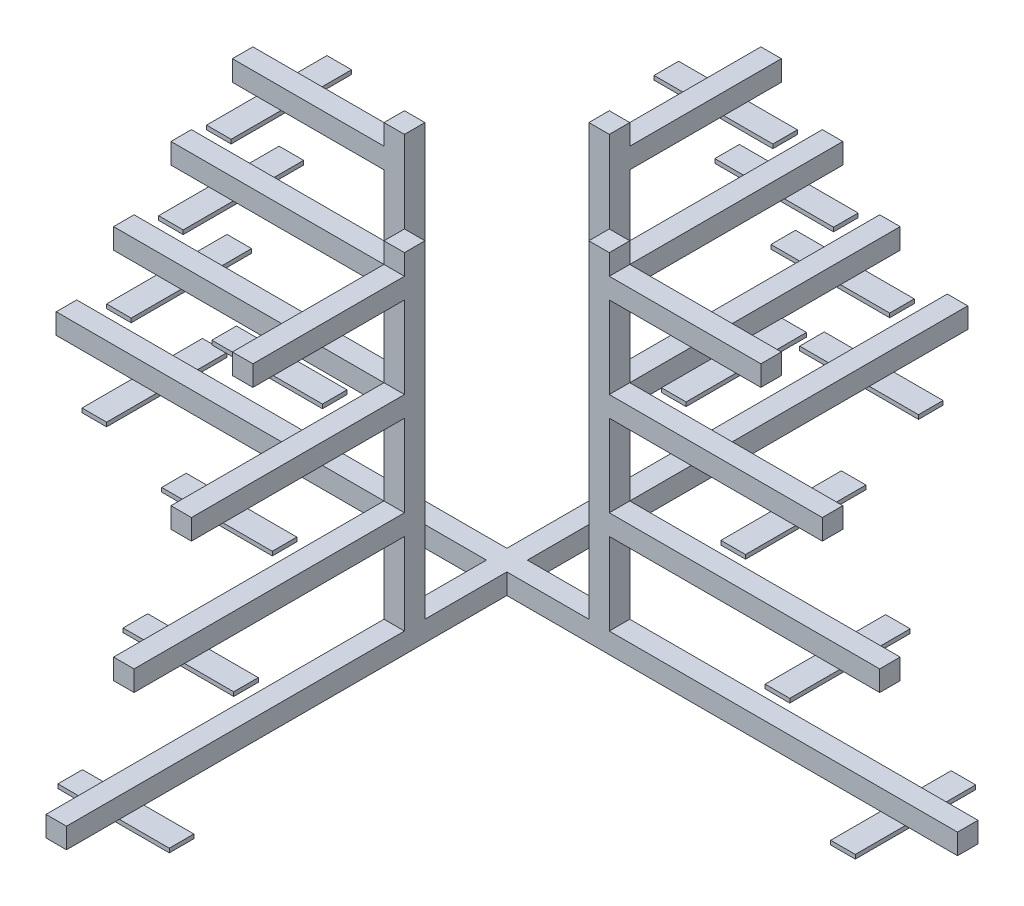
SolidWorks part; units mm, degrees
ref_plane "Front Plane" through (0, 0, 0) normal (0, 0, 1) x (1, 0, 0)
ref_plane "Top Plane" through (0, 0, 0) normal (0, 1, 0) x (1, 0, 0)
ref_plane "Right Plane" through (0, 0, 0) normal (1, 0, 0) x (0, 0, -1)
sketch "Sketch3" plane through (0, 0, 0) normal (0, 0, 1) x (1, 0, 0)
  line L1 (-12.5, 12.5) -> (12.5, 12.5)
  line L2 (-12.5, 12.5) -> (-12.5, -12.5)
  line L3 (-12.5, -12.5) -> (12.5, -12.5)
  line L4 (12.5, 12.5) -> (12.5, -12.5)
  line L5 (-12.5, 12.5) -> (12.5, -12.5) construction
  line L6 (-12.5, -12.5) -> (12.5, 12.5) construction
  point P0 (0, 0)
  dimension "D1" = 25
  dimension "D2" = 25
extrude "Boss-Extrude2" add sketch "Sketch3" along normal mid plane 1100
sketch "Sketch5" plane through (12.5, 0, 0) normal (1, 0, 0) x (0, 0, -1)
  line L0 (-550, -12.5) -> (550, -12.5) construction
  line L1 (-12.5, 12.5) -> (12.5, 12.5)
  line L2 (-12.5, 12.5) -> (-12.5, -12.5)
  line L3 (-12.5, -12.5) -> (12.5, -12.5)
  line L4 (12.5, 12.5) -> (12.5, -12.5)
  line L5 (-12.5, 12.5) -> (12.5, -12.5) construction
  line L6 (-12.5, -12.5) -> (12.5, 12.5) construction
  point P0 (0, 0)
  dimension "D1" = 25
extrude "Boss-Extrude3" add sketch "Sketch5" along normal mid plane 1100
sketch "Sketch7" plane through (0, 12.5, 0) normal (0, 1, 0) x (1, 0, 0)
  line L0 (-12.5, -12.5) -> (12.5, -12.5) construction
  line L1 (12.5, -12.5) -> (12.5, 12.5) construction
  line L2 (12.5, 12.5) -> (-12.5, 12.5) construction
  line L3 (-12.5, 12.5) -> (-12.5, -12.5) construction
  line L4 (-12.5, -12.5) -> (-12.5, -112.5)
  line L5 (-12.5, -550) -> (-12.5, -12.5) construction
  line L6 (-12.5, 12.5) -> (-12.5, 112.5)
  line L7 (-12.5, 12.5) -> (-12.5, 550) construction
  line L8 (-12.5, 112.5) -> (12.5, 112.5)
  line L9 (12.5, 12.5) -> (12.5, 550) construction
  line L10 (12.5, 112.5) -> (12.5, 137.5)
  line L11 (12.5, 137.5) -> (-12.5, 137.5)
  line L12 (-12.5, 137.5) -> (-12.5, 112.5)
  line L13 (-12.5, -112.5) -> (12.5, -112.5)
  line L14 (12.5, -550) -> (12.5, -12.5) construction
  line L15 (12.5, -112.5) -> (12.5, -137.5)
  line L16 (12.5, -137.5) -> (-12.5, -137.5)
  line L17 (-12.5, -137.5) -> (-12.5, -112.5)
  line M11 (12.5, -550) -> (12.5, -12.5)
  line M15 (12.5, 12.5) -> (12.5, 550)
  line M17 (-12.5, 550) -> (-12.5, 12.5)
  line M21 (-12.5, -12.5) -> (-12.5, -550)
  dimension "D1" = 100
  dimension "D2" = 100
  dimension "D3" = 25
  dimension "D4" = 25
extrude "Boss-Extrude4" add sketch "Sketch7" along normal blind 400 contours L16 L13 M11 M21 | L11 L8 M15 M17 region at (0, 12.5, -125) region at (0, 12.5, 125)
sketch "Sketch8" plane through (0, 12.5, 0) normal (0, 1, 0) x (1, 0, 0)
  line L0 (-12.5, -12.5) -> (-112.5, -12.5)
  line L1 (-12.5, -12.5) -> (-537.5, -12.5) construction
  line L2 (12.5, -12.5) -> (112.5, -12.5)
  line L3 (562.5, -12.5) -> (12.5, -12.5) construction
  line L4 (-112.5, -12.5) -> (-112.5, 12.5)
  line L5 (-12.5, 12.5) -> (-537.5, 12.5) construction
  line L6 (-112.5, 12.5) -> (-137.5, 12.5)
  line L7 (-137.5, 12.5) -> (-137.5, -12.5)
  line L8 (-137.5, -12.5) -> (-112.5, -12.5)
  line L9 (112.5, -12.5) -> (112.5, 12.5)
  line L10 (562.5, 12.5) -> (12.5, 12.5) construction
  line L11 (112.5, 12.5) -> (137.5, 12.5)
  line L12 (137.5, 12.5) -> (137.5, -12.5)
  line L13 (137.5, -12.5) -> (112.5, -12.5)
  line M8 (12.5, -12.5) -> (562.5, -12.5)
  line M10 (562.5, 12.5) -> (12.5, 12.5)
  line M14 (-12.5, 12.5) -> (-537.5, 12.5)
  line M16 (-537.5, -12.5) -> (-12.5, -12.5)
  dimension "D1" = 100
  dimension "D2" = 100
  dimension "D3" = 25
  dimension "D4" = 25
extrude "Boss-Extrude5" add sketch "Sketch8" along normal blind 400 contours L12 L9 M10 M8 | L7 L4 M14 M16 region at (-125, 12.5, 0) region at (125, 12.5, 0)
sketch "Sketch9" plane through (0, 0, 137.5) normal (0, 0, 1) x (1, 0, 0)
  line L0 (12.5, 12.5) -> (12.5, 112.5)
  line L1 (12.5, 412.5) -> (12.5, 12.5) construction
  line L2 (12.5, 112.5) -> (-12.5, 112.5)
  line L3 (-12.5, 412.5) -> (-12.5, 12.5) construction
  line L4 (-12.5, 112.5) -> (-12.5, 137.5)
  line L5 (-12.5, 137.5) -> (12.5, 137.5)
  line L6 (12.5, 137.5) -> (12.5, 112.5)
  line L7 (12.5, 137.5) -> (12.5, 237.5)
  line L8 (12.5, 237.5) -> (-12.5, 237.5)
  line L9 (-12.5, 237.5) -> (-12.5, 262.5)
  line L10 (-12.5, 262.5) -> (12.5, 262.5)
  line L11 (12.5, 262.5) -> (12.5, 237.5)
  line L12 (12.5, 262.5) -> (12.5, 362.5)
  line L13 (12.5, 362.5) -> (-12.5, 362.5)
  line L14 (-12.5, 362.5) -> (-12.5, 387.5)
  line L15 (-12.5, 387.5) -> (12.5, 387.5)
  line L16 (12.5, 387.5) -> (12.5, 362.5)
  line L17 (12.5, 262.5) -> (12.5, 237.5)
  line M17 (12.5, 12.5) -> (12.5, 412.5)
  line M19 (-12.5, 412.5) -> (-12.5, 12.5)
  dimension "D1" = 100
  dimension "D2" = 25
  dimension "D3" = 100
  dimension "D4" = 25
  dimension "D5" = 100
  dimension "D6" = 25
extrude "Boss-Extrude7" add sketch "Sketch9" along normal blind 260 contours L10 L8 M19 M17 region at (0, 250, 137.5)
extrude "Boss-Extrude8" add sketch "Sketch9<5>" along normal blind 330 contours L5 L2 M19 M17 region at (0, 125, 137.5)
sketch "Sketch9<5>" plane through (0, 0, 137.5) normal (0, 0, 1) x (1, 0, 0) same geometry as "Sketch9"
extrude "Boss-Extrude10" add sketch "Sketch9<8>" along normal blind 185 contours L15 L13 M19 M17 region at (0, 375, 137.5)
sketch "Sketch9<8>" plane through (0, 0, 137.5) normal (0, 0, 1) x (1, 0, 0) same geometry as "Sketch9"
sketch "Sketch11" plane through (-137.5, 0, 0) normal (-1, 0, 0) x (0, 0, 1)
  line L0 (12.5, 12.5) -> (12.5, 112.5)
  line L1 (12.5, 412.5) -> (12.5, 12.5) construction
  line L2 (12.5, 112.5) -> (-12.5, 112.5)
  line L3 (-12.5, 412.5) -> (-12.5, 12.5) construction
  line L4 (-12.5, 112.5) -> (-12.5, 137.5)
  line L5 (-12.5, 137.5) -> (12.5, 137.5)
  line L6 (12.5, 137.5) -> (12.5, 112.5)
  line L7 (12.5, 137.5) -> (12.5, 237.5)
  line L8 (12.5, 237.5) -> (-12.5, 237.5)
  line L9 (-12.5, 237.5) -> (-12.5, 262.5)
  line L10 (-12.5, 262.5) -> (12.5, 262.5)
  line L11 (12.5, 262.5) -> (12.5, 237.5)
  line L12 (12.5, 362.5) -> (-12.5, 362.5)
  line L13 (-12.5, 362.5) -> (-12.5, 387.5)
  line L14 (-12.5, 387.5) -> (12.5, 387.5)
  line L15 (12.5, 387.5) -> (12.5, 362.5)
  line M16 (12.5, 12.5) -> (12.5, 412.5)
  line M18 (-12.5, 412.5) -> (-12.5, 12.5)
  dimension "D1" = 100
  dimension "D2" = 25
  dimension "D3" = 100
  dimension "D4" = 25
  dimension "D5" = 25
  dimension "D6" = 100
extrude "Boss-Extrude11" add sketch "Sketch11" along normal blind 185 contours L14 L12 M18 M16 region at (-137.5, 375, 0)
extrude "Boss-Extrude12" add sketch "Sketch11<5>" along normal blind 260 contours L10 L8 M18 M16 region at (-137.5, 250, 0)
sketch "Sketch11<5>" plane through (-137.5, 0, 0) normal (-1, 0, 0) x (0, 0, 1) same geometry as "Sketch11"
extrude "Boss-Extrude13" add sketch "Sketch11<6>" along normal blind 330 contours L5 L2 M18 M16 region at (-137.5, 125, 0)
sketch "Sketch11<6>" plane through (-137.5, 0, 0) normal (-1, 0, 0) x (0, 0, 1) same geometry as "Sketch11"
sketch "Sketch12" plane through (0, 0, -137.5) normal (0, 0, -1) x (-1, 0, 0)
  line L0 (12.5, 112.5) -> (-12.5, 112.5)
  line L2 (12.5, 137.5) -> (-12.5, 137.5)
  line L3 (-12.5, 137.5) -> (-12.5, 112.5)
  line L4 (12.5, 137.5) -> (12.5, 112.5)
  line L5 (12.5, 237.5) -> (-12.5, 237.5)
  line L6 (-12.5, 412.5) -> (-12.5, 12.5) construction
  line L7 (-12.5, 237.5) -> (-12.5, 262.5)
  line L8 (-12.5, 262.5) -> (12.5, 262.5)
  line L9 (12.5, 262.5) -> (12.5, 237.5)
  line L10 (12.5, 362.5) -> (-12.5, 362.5)
  line L11 (-12.5, 362.5) -> (-12.5, 387.5)
  line L12 (-12.5, 387.5) -> (12.5, 387.5)
  line L13 (12.5, 387.5) -> (12.5, 362.5)
  line M2 (12.5, 12.5) -> (12.5, 412.5)
  line M4 (-12.5, 412.5) -> (-12.5, 12.5)
extrude "Boss-Extrude14" add sketch "Sketch12" along normal blind 185 contours L12 L10 M4 M2 region at (0, 375, -137.5)
extrude "Boss-Extrude15" add sketch "Sketch12<3>" along normal blind 260 contours L8 L5 M4 M2 region at (0, 250, -137.5)
sketch "Sketch12<3>" plane through (0, 0, -137.5) normal (0, 0, -1) x (-1, 0, 0) same geometry as "Sketch12"
extrude "Boss-Extrude16" add sketch "Sketch12<4>" along normal blind 330 contours L2 L0 M2 M4 region at (0, 125, -137.5)
sketch "Sketch12<4>" plane through (0, 0, -137.5) normal (0, 0, -1) x (-1, 0, 0) same geometry as "Sketch12"
sketch "Sketch13" plane through (137.5, 0, 0) normal (1, 0, 0) x (0, 0, -1)
  line L0 (12.5, 112.5) -> (-12.5, 112.5)
  line L1 (-12.5, 412.5) -> (-12.5, 12.5) construction
  line L2 (-12.5, 112.5) -> (-12.5, 137.5)
  line L3 (-12.5, 137.5) -> (12.5, 137.5)
  line L4 (12.5, 412.5) -> (12.5, 12.5) construction
  line L5 (12.5, 137.5) -> (12.5, 112.5)
  line L6 (12.5, 237.5) -> (12.5, 262.5)
  line L7 (12.5, 262.5) -> (-12.5, 262.5)
  line L8 (-12.5, 262.5) -> (-12.5, 237.5)
  line L9 (-12.5, 237.5) -> (12.5, 237.5)
  line L10 (-12.5, 362.5) -> (12.5, 362.5)
  line L11 (12.5, 362.5) -> (12.5, 387.5)
  line L12 (12.5, 387.5) -> (-12.5, 387.5)
  line L13 (-12.5, 387.5) -> (-12.5, 362.5)
  line M6 (12.5, 12.5) -> (12.5, 412.5)
  line M8 (-12.5, 412.5) -> (-12.5, 12.5)
extrude "Boss-Extrude17" add sketch "Sketch13" along normal blind 330 contours L3 L0 M8 M6 region at (137.5, 125, 0)
extrude "Boss-Extrude18" add sketch "Sketch13<3>" along normal blind 260 contours L9 L7 M8 M6 region at (137.5, 250, 0)
sketch "Sketch13<3>" plane through (137.5, 0, 0) normal (1, 0, 0) x (0, 0, -1) same geometry as "Sketch13"
extrude "Boss-Extrude19" add sketch "Sketch13<4>" along normal blind 185 contours L12 L13 L10 L11
sketch "Sketch13<4>" plane through (137.5, 0, 0) normal (1, 0, 0) x (0, 0, -1) same geometry as "Sketch13"
sketch "Sketch15" plane through (12.5, 0, 0) normal (1, 0, 0) x (0, 0, -1)
  line L0 (-485.5198, -12.5) -> (-485.5198, -17.5)
  line L1 (-550, -12.5) -> (-12.5, -12.5) construction
  line L2 (-485.5198, -17.5) -> (-455.5198, -17.5)
  line L3 (-455.5198, -17.5) -> (-455.5198, -12.5)
  line L4 (-455.5198, -12.5) -> (-485.5198, -12.5)
  dimension "D1" = 5
  dimension "D2" = 30
extrude "Boss-Extrude21" add sketch "Sketch15" along normal blind 61 and the other way blind 75
sketch "Sketch16" plane through (12.5, 0, 0) normal (1, 0, 0) x (0, 0, -1)
  line L0 (-405.908, 112.5) -> (-405.908, 107.5)
  line L1 (-467.5, 112.5) -> (-137.5, 112.5) construction
  line L2 (-405.908, 107.5) -> (-375.908, 107.5)
  line L3 (-375.908, 107.5) -> (-375.908, 112.5)
  line L4 (-375.908, 112.5) -> (-405.908, 112.5)
  line L5 (-358.8325, 237.5) -> (-358.8325, 232.5)
  line L6 (-397.5, 237.5) -> (-137.5, 237.5) construction
  line L7 (-358.8325, 232.5) -> (-328.8325, 232.5)
  line L8 (-328.8325, 232.5) -> (-328.8325, 237.5)
  line L9 (-328.8325, 237.5) -> (-358.8325, 237.5)
  line L10 (-297.5952, 362.5) -> (-297.5952, 357.5)
  line L11 (-322.5, 362.5) -> (-137.5, 362.5) construction
  line L12 (-297.5952, 357.5) -> (-267.5952, 357.5)
  line L13 (-267.5952, 357.5) -> (-267.5952, 362.5)
  line L14 (-267.5952, 362.5) -> (-297.5952, 362.5)
  dimension "D1" = 5
  dimension "D2" = 30
  dimension "D3" = 30
  dimension "D4" = 5
  dimension "D5" = 30
  dimension "D6" = 5
extrude "Boss-Extrude22" add sketch "Sketch16" along normal blind 60 and the other way blind 75
sketch "Sketch18" plane through (0, 0, 12.5) normal (0, 0, 1) x (1, 0, 0)
  line L0 (498.7274, -12.5) -> (498.7274, -17.5)
  line L1 (562.5, -12.5) -> (12.5, -12.5) construction
  line L2 (498.7274, -17.5) -> (468.7274, -17.5)
  line L3 (468.7274, -17.5) -> (468.7274, -12.5)
  line L4 (468.7274, -12.5) -> (498.7274, -12.5)
  line L5 (418.7448, 112.5) -> (418.7448, 107.5)
  line L6 (467.5, 112.5) -> (137.5, 112.5) construction
  line L7 (418.7448, 107.5) -> (388.7448, 107.5)
  line L8 (388.7448, 107.5) -> (388.7448, 112.5)
  line L9 (388.7448, 112.5) -> (418.7448, 112.5)
  line L10 (364.7545, 237.5) -> (364.7545, 232.5)
  line L11 (397.5, 237.5) -> (137.5, 237.5) construction
  line L12 (364.7545, 232.5) -> (334.7545, 232.5)
  line L13 (334.7545, 232.5) -> (334.7545, 237.5)
  line L14 (334.7545, 237.5) -> (364.7545, 237.5)
  line L15 (292.1874, 362.5) -> (292.1874, 357.5)
  line L16 (322.5, 362.5) -> (137.5, 362.5) construction
  line L17 (292.1874, 357.5) -> (262.1874, 357.5)
  line L18 (262.1874, 357.5) -> (262.1874, 362.5)
  line L19 (262.1874, 362.5) -> (292.1874, 362.5)
  dimension "D1" = 30
  dimension "D2" = 5
  dimension "D3" = 30
  dimension "D4" = 5
  dimension "D5" = 30
  dimension "D6" = 5
  dimension "D7" = 30
  dimension "D8" = 5
extrude "Boss-Extrude23" add sketch "Sketch18" along normal blind 61 and the other way blind 86
sketch "Sketch19" plane through (12.5, 0, 0) normal (1, 0, 0) x (0, 0, -1)
  line L0 (459.862, -12.5) -> (459.862, -17.5)
  line L1 (12.5, -12.5) -> (550, -12.5) construction
  line L2 (459.862, -17.5) -> (429.862, -17.5)
  line L3 (429.862, -17.5) -> (429.862, -12.5)
  line L4 (429.862, -12.5) -> (459.862, -12.5)
  line L5 (424.7264, 112.5) -> (424.7264, 107.5)
  line L6 (467.5, 112.5) -> (137.5, 112.5) construction
  line L7 (424.7264, 107.5) -> (394.7264, 107.5)
  line L8 (394.7264, 107.5) -> (394.7264, 112.5)
  line L9 (394.7264, 112.5) -> (424.7264, 112.5)
  line L10 (356.2491, 237.5) -> (356.2491, 232.5)
  line L11 (397.5, 237.5) -> (137.5, 237.5) construction
  line L12 (356.2491, 232.5) -> (326.2491, 232.5)
  line L13 (326.2491, 232.5) -> (326.2491, 237.5)
  line L14 (326.2491, 237.5) -> (356.2491, 237.5)
  line L15 (282.1005, 362.5) -> (282.1005, 357.5)
  line L16 (322.5, 362.5) -> (137.5, 362.5) construction
  line L17 (282.1005, 357.5) -> (252.1005, 357.5)
  line L18 (252.1005, 357.5) -> (252.1005, 362.5)
  line L19 (252.1005, 362.5) -> (282.1005, 362.5)
  dimension "D1" = 5
  dimension "D2" = 30
  dimension "D3" = 30
  dimension "D4" = 5
  dimension "D5" = 30
  dimension "D6" = 5
  dimension "D7" = 30
  dimension "D8" = 5
extrude "Boss-Extrude24" add sketch "Sketch19" along normal blind 60 and the other way blind 85
sketch "Sketch20" plane through (0, 0, -12.5) normal (0, 0, -1) x (-1, 0, 0)
  line L0 (445.0666, -12.5) -> (445.0666, -17.5)
  line L1 (12.5, -12.5) -> (537.5, -12.5) construction
  line L2 (445.0666, -17.5) -> (415.0666, -17.5)
  line L3 (415.0666, -17.5) -> (415.0666, -12.5)
  line L4 (415.0666, -12.5) -> (445.0666, -12.5)
  line L5 (415.0666, 112.5) -> (415.0666, 107.5)
  line L6 (467.5, 112.5) -> (137.5, 112.5) construction
  line L7 (415.0666, 107.5) -> (385.0666, 107.5)
  line L8 (385.0666, 107.5) -> (385.0666, 112.5)
  line L9 (385.0666, 112.5) -> (415.0666, 112.5)
  line L10 (351.5406, 237.5) -> (351.5406, 232.5)
  line L11 (397.5, 237.5) -> (137.5, 237.5) construction
  line L12 (351.5406, 232.5) -> (321.5406, 232.5)
  line L13 (321.5406, 232.5) -> (321.5406, 237.5)
  line L14 (321.5406, 237.5) -> (351.5406, 237.5)
  line L15 (293.0602, 362.5) -> (293.0602, 357.5)
  line L16 (322.5, 362.5) -> (137.5, 362.5) construction
  line L17 (293.0602, 357.5) -> (263.0602, 357.5)
  line L18 (263.0602, 357.5) -> (263.0602, 362.5)
  line L19 (263.0602, 362.5) -> (293.0602, 362.5)
  dimension "D1" = 30
  dimension "D2" = 5
  dimension "D3" = 30
  dimension "D4" = 5
  dimension "D5" = 30
  dimension "D6" = 5
  dimension "D7" = 30
  dimension "D8" = 5
extrude "Boss-Extrude27" add sketch "Sketch20" along normal blind 61 and the other way blind 86
